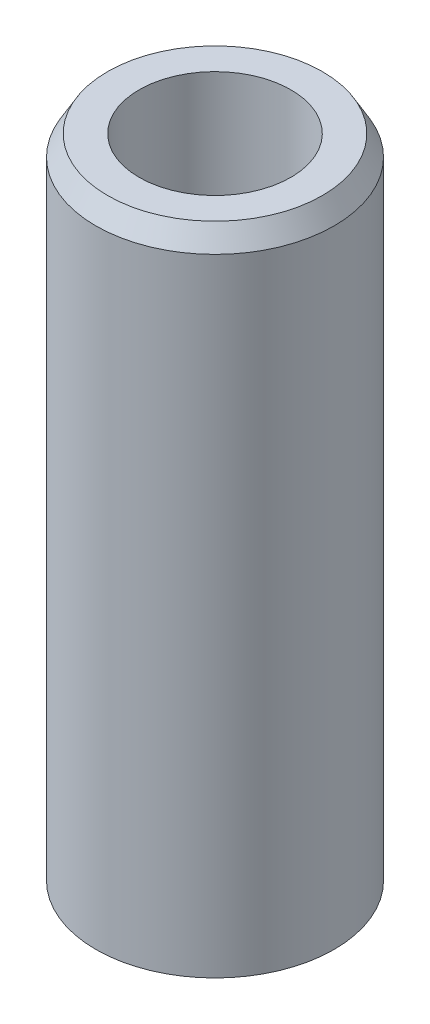
SolidWorks part; units mm, degrees
ref_plane "Front Plane" through (0, 0, 0) normal (0, 0, 1) x (1, 0, 0)
ref_plane "Top Plane" through (0, 0, 0) normal (0, 1, 0) x (1, 0, 0)
ref_plane "Right Plane" through (0, 0, 0) normal (1, 0, 0) x (0, 0, -1)
sketch "Sketch1" plane through (0, 0, 0) normal (0, 1, 0) x (1, 0, 0)
  circle A0 centre (0, 0) radius 17.5
  dimension "SHAFT_OD" = 35
extrude "Boss-Extrude1" add sketch "Sketch1" along normal blind 96.7496
sketch "Sketch2" plane through (0, 0, 0) normal (0, 1, 0) x (1, 0, 0)
  circle A0 centre (0, 0) radius 11.1463
  dimension "BORE_D" = 22.2925
extrude "Cut-Extrude1" cut sketch "Sketch2" along normal through all
chamfer "Chamfer1" distance 2.9946 angle 30 2 edges at (0, 96.7496, 17.5) (0, 0, 17.5) first distance on face at (0, 96.7496, 17.5) first distance on face at (0, 0, 11.1463)
